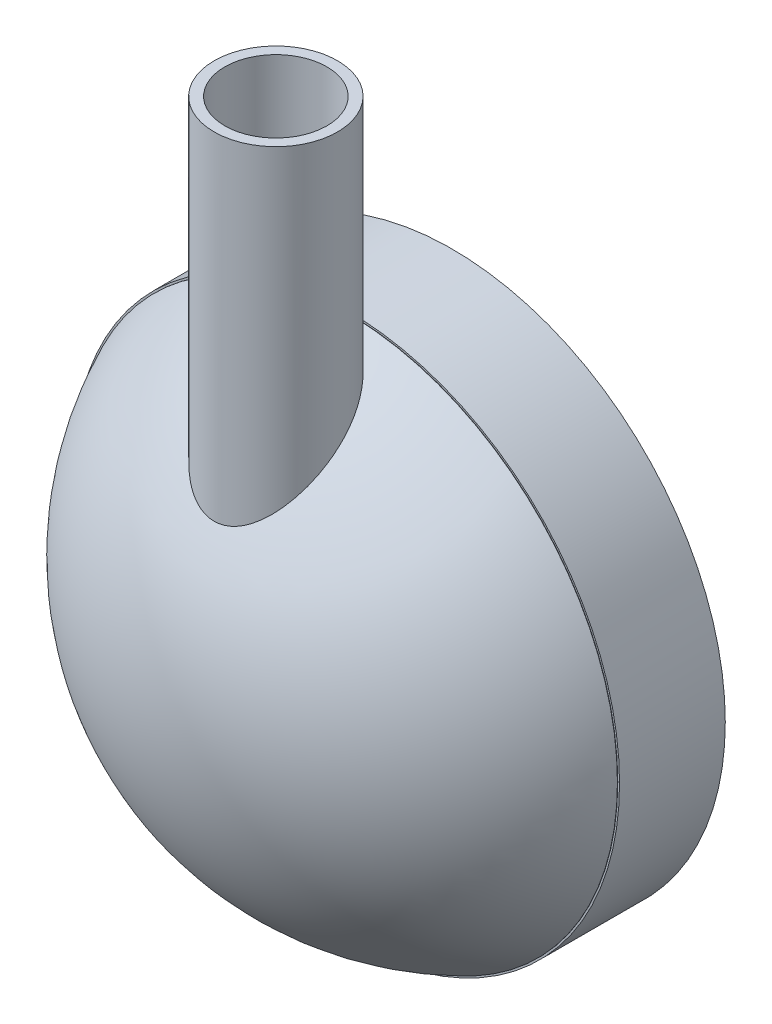
SolidWorks part; units mm, degrees
ref_plane "Front Plane" through (0, 0, 0) normal (0, 0, 1) x (1, 0, 0)
ref_plane "Top Plane" through (0, 0, 0) normal (0, 1, 0) x (1, 0, 0)
ref_plane "Right Plane" through (0, 0, 0) normal (1, 0, 0) x (0, 0, -1)
sketch "Sketch1" plane through (0, 0, 0) normal (0, 0, 1) x (1, 0, 0)
  circle A0 centre (0, 0) radius 77.5
  dimension "D1" = 155
extrude "Boss-Extrude1" add sketch "Sketch1" along normal blind 30
sketch "Sketch2" plane through (0, 0, 30) normal (0, 0, 1) x (1, 0, 0)
  circle A0 centre (0, 0) radius 77
  dimension "D1" = 154
extrude "Boss-Extrude2" add sketch "Sketch2" along normal blind 0.1
dome "Dome1" faces to dome 1 distance 50 reverse direction no elliptical dome no face at (77, 0, 30.1) parameters "D1"=50
dome "Dome2" faces to dome 1 distance 15 reverse direction no elliptical dome no face at (77.5, 0, 0) parameters "D1"=15
sketch "Sketch3" plane through (0, 0, 0) normal (0, 1, 0) x (1, 0, 0)
  line L0 (77.5, 0) -> (-77.5, 0) construction
  line L1 (-77.5, 0) -> (-77.5, -30) construction
  circle A0 centre (0, -50) radius 17.5
  point P5 (0, 0)
  dimension "D1" = 35
  dimension "D2" = 50
  dimension "D3" = 77.5
extrude "Boss-Extrude3" add sketch "Sketch3" along normal blind 140
shell "Shell1" thickness 3 removed face at (0, 140, 67.5)
